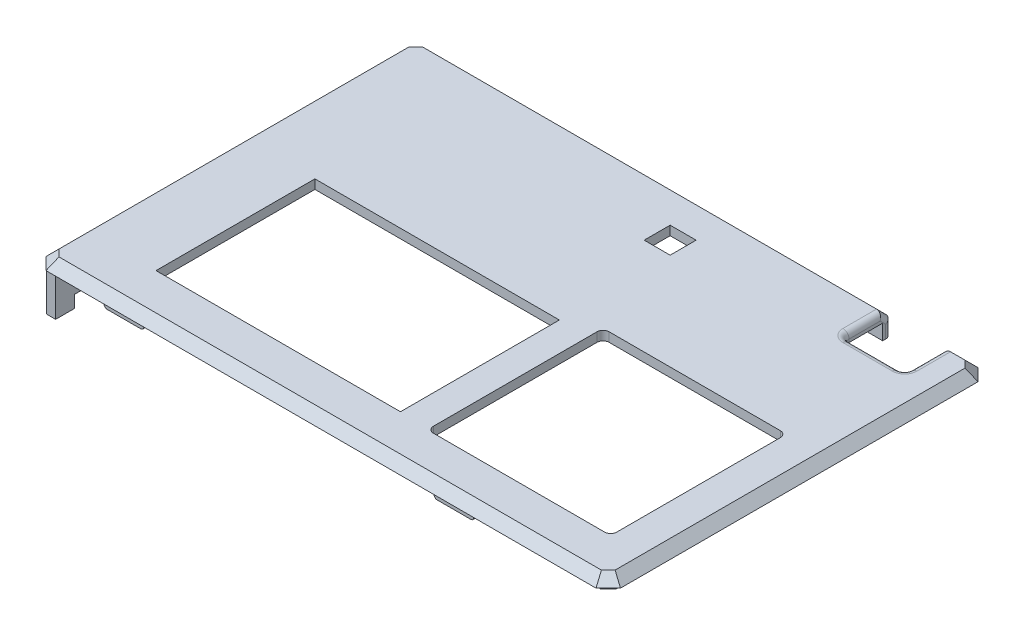
SolidWorks part; units mm, degrees
material "尼龙 101"
ref_plane "前视基准面" through (0, 0, 0) normal (0, 0, 1) x (1, 0, 0)
ref_plane "上视基准面" through (0, 0, 0) normal (0, 1, 0) x (1, 0, 0)
ref_plane "右视基准面" through (0, 0, 0) normal (1, 0, 0) x (0, 0, -1)
sketch "草图1" plane through (0, 0, 0) normal (0, 1, 0) x (1, 0, 0)
  line L1 (94, -62.5) -> (-94, -62.5)
  line L2 (94, -62.5) -> (94, 62.5)
  line L3 (94, 62.5) -> (-94, 62.5)
  line L4 (-94, -62.5) -> (-94, 62.5)
  line L5 (94, -62.5) -> (-94, 62.5) construction
  line L6 (94, 62.5) -> (-94, -62.5) construction
  point P0 (0, 0)
  dimension "D1" = 188
  dimension "D2" = 125
extrude "凸台-拉伸1" add sketch "草图1" against normal blind 3
sketch "草图2" plane through (0, -3, 0) normal (0, -1, 0) x (1, 0, 0)
  line L0 (-94, 62.5) -> (94, 62.5) construction
  line L1 (-74, 57.5) -> (-61, 57.5)
  line L2 (-74, 57.5) -> (-74, 59.5)
  line L3 (-74, 59.5) -> (-61, 59.5)
  line L4 (-61, 57.5) -> (-61, 59.5)
  line L5 (34, 57.5) -> (47, 57.5)
  line L6 (34, 57.5) -> (34, 59.5)
  line L7 (34, 59.5) -> (47, 59.5)
  line L8 (47, 57.5) -> (47, 59.5)
  line L9 (-94, -62.5) -> (-94, 62.5) construction
  line L10 (94, 62.5) -> (94, -62.5) construction
  line L11 (-94, 0) -> (94, 0) construction
  line L12 (34, -59.5) -> (47, -59.5)
  line L13 (47, -57.5) -> (47, -59.5)
  line L14 (34, -57.5) -> (47, -57.5)
  line L15 (34, -57.5) -> (34, -59.5)
  line L16 (-74, -59.5) -> (-61, -59.5)
  line L17 (-61, -57.5) -> (-61, -59.5)
  line L18 (-74, -57.5) -> (-61, -57.5)
  line L19 (-74, -57.5) -> (-74, -59.5)
  point P10 (-74, 58.5)
  dimension "D1" = 2
  dimension "D2" = 13
  dimension "D3" = 13
  dimension "D4" = 2
  dimension "D5" = 3
  dimension "D6" = 3
  dimension "D7" = 20
  dimension "D8" = 47
extrude "凸台-拉伸2" add sketch "草图2" along normal blind 4
sketch "草图3" plane through (0, 0, 59.5) normal (0, 0, 1) x (1, 0, 0)
  line L0 (-94, -3) -> (94, -3) construction
  line L1 (-72.5, -5.5) -> (-62.5, -5.5)
  line L2 (-72.5, -5.5) -> (-72.5, -4)
  line L3 (-72.5, -4) -> (-62.5, -4)
  line L4 (-62.5, -5.5) -> (-62.5, -4)
  line L5 (-61, -7) -> (-61, -3) construction
  line L6 (47, -3) -> (34, -3) construction
  line L7 (35.5, -5.5) -> (45.5, -5.5)
  line L8 (35.5, -5.5) -> (35.5, -4)
  line L9 (35.5, -4) -> (45.5, -4)
  line L10 (45.5, -5.5) -> (45.5, -4)
  line L11 (34, -7) -> (34, -3) construction
  dimension "D1" = 1.5
  dimension "D2" = 1
  dimension "D3" = 10
  dimension "D4" = 1.5
  dimension "D5" = 1.5
  dimension "D6" = 1
  dimension "D7" = 10
  dimension "D8" = 1.5
extrude "切除-拉伸1" cut sketch "草图3" against normal up to surface (119 mm away) up to face at (40.5, -5, -59.5)
fillet "圆角1" radius 1 8 edges at (-61, -7, 58.5) (-74, -7, 58.5) (34, -7, 58.5) (47, -7, 58.5) (34, -7, -58.5) (47, -7, -58.5) (-61, -7, -58.5) (-74, -7, -58.5)
chamfer "倒角1" distance 4 angle 45 4 edges at (94, -1.5, 62.5) (94, -1.5, -62.5) (-94, -1.5, -62.5) (-94, -1.5, 62.5)
chamfer "倒角2" distance 3 angle 45 8 edges at (92, 0, -60.5) (0, 0, -62.5) (-92, 0, -60.5) (-94, 0, 0) (-92, 0, 60.5) (0, 0, 62.5) (92, 0, 60.5) (94, 0, 0)
sketch "草图4" plane through (0, -3, 0) normal (0, -1, 0) x (1, 0, 0)
  line L16 (-90, -61) -> (-92.5, -58.5)
  line L17 (91, -59.5) -> (-91, -59.5)
  line L18 (91, -59.5) -> (91, 59.5)
  line L19 (91, 59.5) -> (-91, 59.5)
  line L20 (-91, -59.5) -> (-91, 59.5)
  line L21 (91, -59.5) -> (-91, 59.5) construction
  line L22 (91, 59.5) -> (-91, -59.5) construction
  line L23 (90, -61) -> (-90, -61)
  line L24 (92.5, -58.5) -> (92.5, 58.5)
  line L25 (90, 61) -> (-90, 61)
  line L26 (-92.5, -58.5) -> (-92.5, 58.5)
  line L27 (92.5, -61) -> (-92.5, 61) construction
  line L28 (92.5, 61) -> (-92.5, -61) construction
  line L29 (-90, 61) -> (-92.5, 58.5)
  line L30 (92.5, 58.5) -> (90, 61)
  line L31 (92.5, -58.5) -> (90, -61)
  point P0 (0, 0)
  point P5 (0, 0)
  dimension "D1" = 182
  dimension "D2" = 119
  dimension "D3" = 185
  dimension "D4" = 122
extrude "凸台-拉伸3" add sketch "草图4" along normal blind 1
chamfer "倒角3" distance 2 angle 45 4 edges at (-91, -3.5, -59.5) (91, -3.5, -59.5) (91, -3.5, 59.5) (-91, -3.5, 59.5)
sketch "草图5" plane through (0, 0, 0) normal (0, 1, 0) x (1, 0, 0)
  line L0 (-91, 57.2574) -> (-91, -57.2574) construction
  line L1 (-76, -56.5) -> (17, -56.5) construction
  line L2 (-76, -56.5) -> (-76, 13.5) construction
  line L3 (-76, 13.5) -> (17, 13.5) construction
  line L4 (17, -56.5) -> (17, 13.5) construction
  line L5 (-91, 57.2574) -> (-91, -57.2574) construction
  line L6 (91, -57.2574) -> (91, 57.2574) construction
  line L7 (91, -57.2574) -> (91, 57.2574) construction
  line L8 (88.7574, 59.5) -> (-88.7574, 59.5) construction
  line L9 (88.7574, 59.5) -> (-88.7574, 59.5) construction
  line L10 (-88.7574, -59.5) -> (88.7574, -59.5) construction
  line L11 (-88.7574, -59.5) -> (88.7574, -59.5) construction
  line L12 (18, -51.2) -> (83, -51.2) construction
  line L13 (18, 12.3) -> (83, 12.3) construction
  line L14 (18, 12.3) -> (18, -56.5) construction
  line L15 (18, -56.5) -> (83, -56.5) construction
  line L16 (83, 12.3) -> (83, -56.5) construction
  line L17 (-69, -47.5) -> (11, -47.5)
  line L18 (-69, -47.5) -> (-69, 4.5)
  line L19 (-69, 4.5) -> (11, 4.5)
  line L20 (11, -47.5) -> (11, 4.5)
  line L25 (25.5, 3.3) -> (75.5, 3.3) construction
  line L26 (25.5, 3.3) -> (25.5, -42.2) construction
  line L27 (25.5, -42.2) -> (75.5, -42.2) construction
  line L28 (75.5, 3.3) -> (75.5, -42.2) construction
  line L29 (50.5, 12.3) -> (50.5, -51.2) construction
  line L90 (90, 62.5) -> (-90, 62.5) construction
  line L91 (-5.5, 22) -> (18.5, 22) construction
  line L92 (-5.5, 22) -> (-5.5, 58.5) construction
  line L93 (-5.5, 58.5) -> (18.5, 58.5) construction
  line L94 (18.5, 22) -> (18.5, 58.5) construction
  line L99 (2.25, 41) -> (10.75, 41)
  line L100 (2.25, 41) -> (2.25, 49.5)
  line L101 (2.25, 49.5) -> (10.75, 49.5)
  line L102 (10.75, 41) -> (10.75, 49.5)
  line L103 (61.8, 62.5) -> (82, 62.5)
  line L104 (61.8, 62.5) -> (61.8, 48.5)
  line L105 (63.8, 46.5) -> (80, 46.5)
  line L106 (82, 62.5) -> (82, 48.5)
  line L107 (94, -58.5) -> (94, 58.5) construction
  line L109 (22.5, 9.3) -> (78.5, 9.3)
  line L110 (20.5, 7.3) -> (20.5, -46.2)
  line L111 (22.5, -48.2) -> (78.5, -48.2)
  line L112 (80.5, 7.3) -> (80.5, -46.2)
  arc A0 (78.5, -48.2) -> (80.5, -46.2) centre (78.5, -46.2) ccw
  arc A1 (20.5, -46.2) -> (22.5, -48.2) centre (22.5, -46.2) ccw
  arc A2 (78.5, 9.3) -> (80.5, 7.3) centre (78.5, 7.3) cw
  arc A3 (22.5, 9.3) -> (20.5, 7.3) centre (22.5, 7.3) ccw
  arc A4 (80, 46.5) -> (82, 48.5) centre (80, 48.5) ccw
  arc A5 (61.8, 48.5) -> (63.8, 46.5) centre (63.8, 48.5) ccw
  point P100 (6.5, 58.5)
  point P101 (2.25, 45.25)
  dimension "D13" = 2
  dimension "D14" = 2
  dimension "D1" = 15
  dimension "D2" = 93
  dimension "D3" = 70
  dimension "D4" = 1
  dimension "D5" = 66
  dimension "D6" = 68.8
  dimension "D7" = 3
  dimension "D8" = 3
  dimension "D9" = 80
  dimension "D10" = 52
  dimension "D11" = 9
  dimension "D12" = 7
  dimension "D15" = 50
  dimension "D16" = 45.5
  dimension "D17" = 5.3
  dimension "D18" = 7.5
  dimension "D19" = 9
  dimension "D22" = 85.5
  dimension "D23" = 24
  dimension "D24" = 36.5
  dimension "D25" = 8.5
  dimension "D26" = 9
  dimension "D27" = 8.5
  dimension "D28" = 8.5
  dimension "D29" = 7.75
  dimension "D30" = 12
  dimension "D31" = 20.2
  dimension "D32" = 16
  dimension "D33" = 2.5
  dimension "D34" = 2.5
  dimension "D35" = 3
  dimension "D36" = 3
extrude "切除-拉伸2" cut sketch "草图5" against normal up to next
sketch "草图7" plane through (0, -4, 0) normal (0, -1, 0) x (1, 0, 0)
  line L0 (-92.5, 58.5) -> (-90, 58.5)
  line L1 (-89, 59.5) -> (-91, 57.5) construction
  line L2 (-90, 58.5) -> (-91, 57.5)
  line L3 (-91, 57.5) -> (-91, -57.5)
  line L4 (-91, -57.5) -> (-90, -58.5)
  line L5 (-91, -57.5) -> (-89, -59.5) construction
  line L6 (-90, -58.5) -> (-92.5, -58.5)
  line L7 (-92.5, -58.5) -> (-92.5, 58.5)
extrude "切除-拉伸3" cut sketch "草图7" against normal up to surface (1 mm away) up to face at (6.5, -3, -45.25)
sketch "草图8" plane through (0, -3, 0) normal (0, -1, 0) x (1, 0, 0)
  line L0 (-94, -58.5) -> (-94, 58.5) construction
  line L1 (-94, 58.35) -> (-91, 58.35)
  line L2 (-94, 58.35) -> (-94, -58.35)
  line L3 (-94, -58.35) -> (-91, -58.35)
  line L4 (-91, 58.35) -> (-91, -58.35)
  line L5 (-90, 58.5) -> (-92.5, 58.5) construction
  line L6 (-92.5, -58.5) -> (-90, -58.5) construction
  point P10 (-91.25, 58.5)
  dimension "D1" = 0.15
  dimension "D2" = 0.15
  dimension "D3" = 3
extrude "凸台-拉伸4" add sketch "草图8" along normal blind 16.4
sketch "草图9" plane through (-94, 0, 0) normal (-1, 0, 0) x (0, 0, 1)
  line L0 (58.35, -19.4) -> (-58.35, -19.4) construction
  line L1 (-14.25, -19.4) -> (-4.25, -19.4)
  line L2 (-14.25, -19.4) -> (-14.25, -10.4)
  line L3 (-14.25, -10.4) -> (-4.25, -10.4)
  line L4 (-4.25, -19.4) -> (-4.25, -10.4)
  line L5 (-58.35, -19.4) -> (-58.35, -3) construction
  line L6 (58.35, -19.4) -> (58.35, -3) construction
  line L7 (52.25, -19.4) -> (38.55, -19.4)
  line L8 (52.25, -19.4) -> (52.25, -15.4)
  line L9 (52.25, -15.4) -> (38.55, -15.4)
  line L10 (38.55, -19.4) -> (38.55, -15.4)
  line L11 (0.2, -19.4) -> (0.2, -16.9)
  line L12 (0.2, -16.9) -> (5.2, -16.9)
  line L13 (5.2, -16.9) -> (5.2, -19.4)
  line L14 (0.2, -19.4) -> (5.2, -19.4)
  line L15 (36.5, -19.4) -> (36.5, -17.9)
  line L16 (36.5, -17.9) -> (28, -17.9)
  line L17 (28, -17.9) -> (28, -19.4)
  line L18 (28, -19.4) -> (36.5, -19.4)
  dimension "D1" = 44.1
  dimension "D2" = 9
  dimension "D3" = 10
  dimension "D4" = 6.1
  dimension "D5" = 4
  dimension "D6" = 13.7
  dimension "D7" = 4.45
  dimension "D8" = 5
  dimension "D9" = 2.5
  dimension "D10" = 21.85
  dimension "D11" = 8.5
  dimension "D12" = 1.5
extrude "切除-拉伸4" cut sketch "草图9" against normal up to next
sketch "草图10" plane through (0, -4, 0) normal (0, -1, 0) x (1, 0, 0)
  line L0 (-90, -61) -> (61.8, -61) construction
  line L1 (61.8, -59.5) -> (47.3, -59.5)
  line L2 (61.8, -59.5) -> (61.8, -61)
  line L3 (61.8, -61) -> (47.3, -61)
  line L4 (47.3, -59.5) -> (47.3, -61)
  dimension "D1" = 14.5
extrude "切除-拉伸5" cut sketch "草图10" against normal up to surface (1 mm away) up to face at (-29, -3, 21.5)
sketch "草图11" plane through (0, -3, 0) normal (0, -1, 0) x (1, 0, 0)
  line L1 (61.8, -62.5) -> (47.3034, -62.5)
  line L2 (61.8, -62.5) -> (61.8, -59.5)
  line L3 (61.8, -59.5) -> (47.3034, -59.5)
  line L4 (47.3034, -62.5) -> (47.3034, -59.5)
  dimension "D1" = 3
  dimension "D2" = 14.4966
extrude "凸台-拉伸5" add sketch "草图11" along normal blind 5
fillet "圆角2" radius 2 8 edges at (82, 0, -54) (81.4142, 0, -47.0858) (71.9, 0, -46.5) (62.3858, 0, -47.0858) (82, -1.5, -61) (61.8, -5.5, -62.5) (61.8, -1.5, -61) (61.8, 0, -54)
